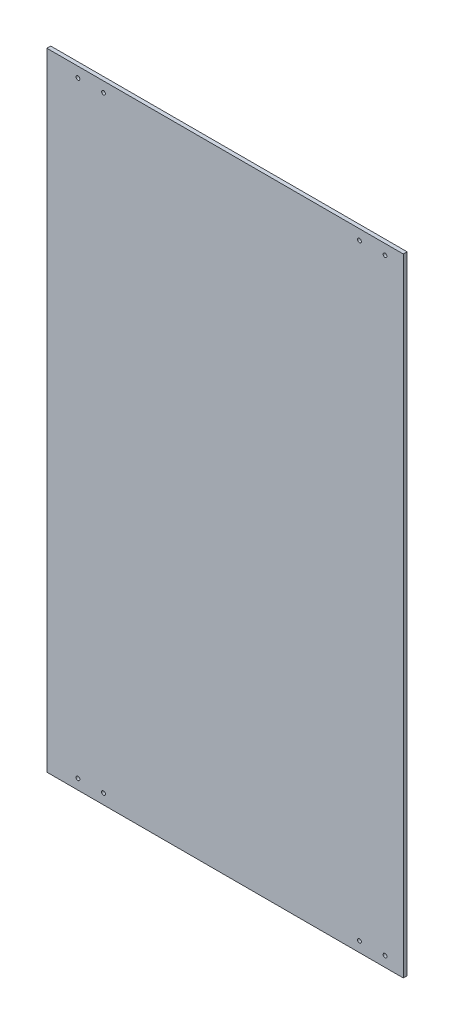
SolidWorks part; units mm, degrees
ref_plane "前视基准面" through (0, 0, 0) normal (0, 0, 1) x (1, 0, 0)
ref_plane "上视基准面" through (0, 0, 0) normal (0, 1, 0) x (1, 0, 0)
ref_plane "右视基准面" through (0, 0, 0) normal (1, 0, 0) x (0, 0, -1)
other "Configuration Table"
sketch "草图1" plane through (0, 0, 0) normal (0, 0, 1) x (1, 0, 0)
  line L0 (-99.3732, -240) -> (-123.3732, -240) construction
  line L1 (-139.28, 245) -> (139.28, 245)
  line L2 (-139.28, 245) -> (-139.28, -245)
  line L3 (-139.28, -245) -> (139.28, -245)
  line L4 (139.28, 245) -> (139.28, -245)
  line L5 (-139.28, 245) -> (139.28, -245) construction
  line L6 (-139.28, -245) -> (139.28, 245) construction
  line L7 (-52.722, -240) -> (-100.722, -240) construction
  line L8 (123.371, -240) -> (99.371, -240) construction
  line L9 (245.0536, 242) -> (105.7724, 242) construction
  line L10 (117.8124, -240) -> (128.3124, -240) construction
  line L11 (-123.3732, 242) -> (-99.3732, 242) construction
  line L12 (-100.722, 242) -> (-52.722, 242) construction
  line L13 (88.4519, 242) -> (105.7724, 242) construction
  circle A0 centre (104.9991, 237) radius 1.5
  circle A1 centre (124.9991, 237) radius 1.5
  circle A2 centre (-95.0009, 237) radius 1.5
  circle A3 centre (-115.0009, 237) radius 1.5
  circle A4 centre (124.9991, -237) radius 1.5
  circle A5 centre (104.9991, -237) radius 1.5
  circle A6 centre (-95.0009, -237) radius 1.5
  circle A7 centre (-115.0009, -237) radius 1.5
  point P0 (0, 0)
  dimension "D3" = 24.2791
  dimension "D4" = 20
  dimension "D6" = 3
  dimension "D9" = 14.2809
  dimension "D1" = 490
  dimension "D2" = 278.56
  dimension "D5" = 3
  dimension "D7" = 3
  dimension "D8" = 20
  dimension "D10" = 3
  dimension "D11" = 24.2791
  dimension "D12" = 5
  dimension "D13" = 5
  dimension "D14" = 20
  dimension "D15" = 20
  dimension "D16" = 14.2809
  dimension "D17" = 5
  dimension "D18" = 5
extrude "凸台-拉伸1" add sketch "草图1" along normal blind 3
